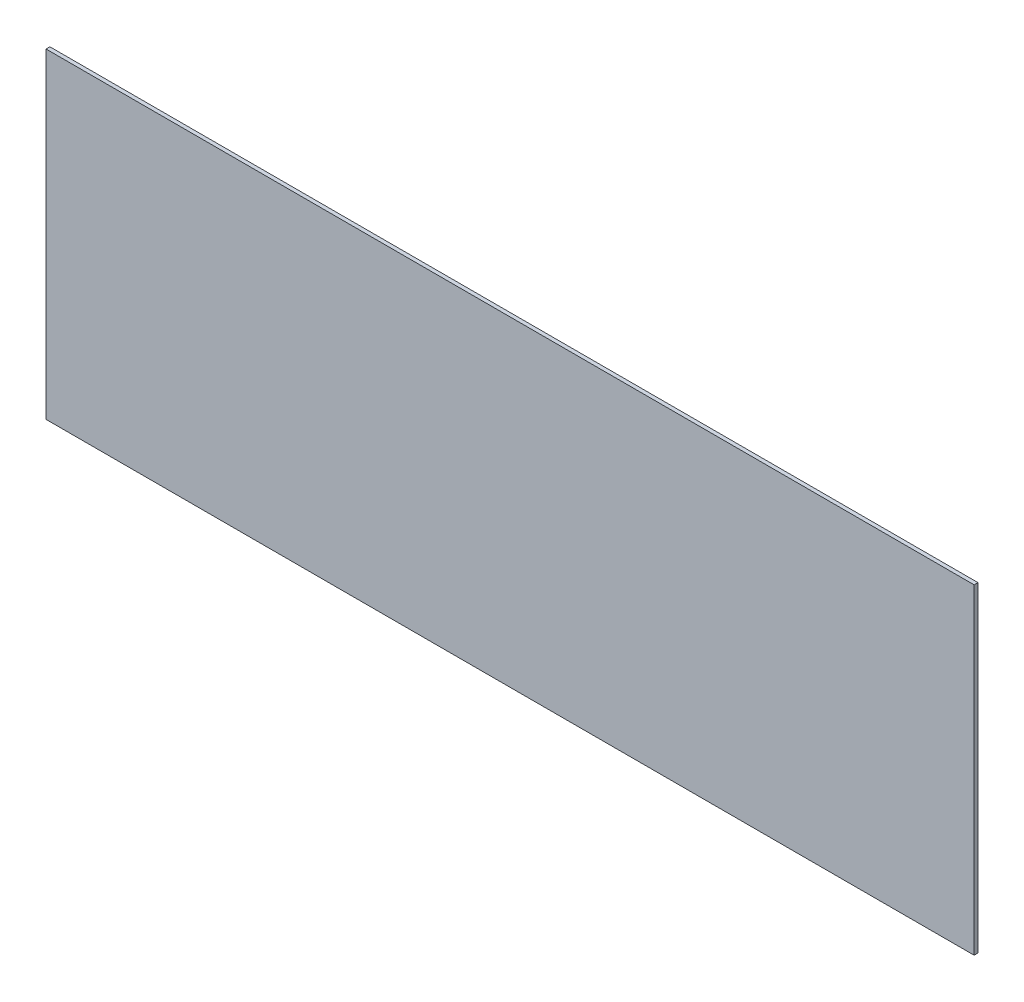
SolidWorks part; units mm, degrees
material "Mahogany"
ref_plane "Front Plane" through (0, 0, 0) normal (0, 0, 1) x (1, 0, 0)
ref_plane "Top Plane" through (0, 0, 0) normal (0, 1, 0) x (1, 0, 0)
ref_plane "Right Plane" through (0, 0, 0) normal (1, 0, 0) x (0, 0, -1)
sketch "Sketch1" plane through (0, 0, 0) normal (0, 0, 1) x (1, 0, 0)
  line L1 (-382.5, 132.2) -> (382.5, 132.2)
  line L2 (-382.5, 132.2) -> (-382.5, -132.2)
  line L3 (-382.5, -132.2) -> (382.5, -132.2)
  line L4 (382.5, 132.2) -> (382.5, -132.2)
  line L5 (-382.5, 132.2) -> (382.5, -132.2) construction
  line L6 (-382.5, -132.2) -> (382.5, 132.2) construction
  point P0 (0, 0)
  dimension "D1" = 765
  dimension "D2" = 264.4
extrude "Boss-Extrude1" add sketch "Sketch1" along normal blind 3.175
equation "\"W\"= 1700"
equation "\"L\"= 780"
equation "\"H\"= 780"
equation "\"ARM_BOLT_SPACING\"= 166"
equation "\"ARM_TO_WALL\"= 200"
equation "\"D1@Sketch1\"=\"L\"-15"
equation "\"D2@Sketch1\"=279.4-15"
